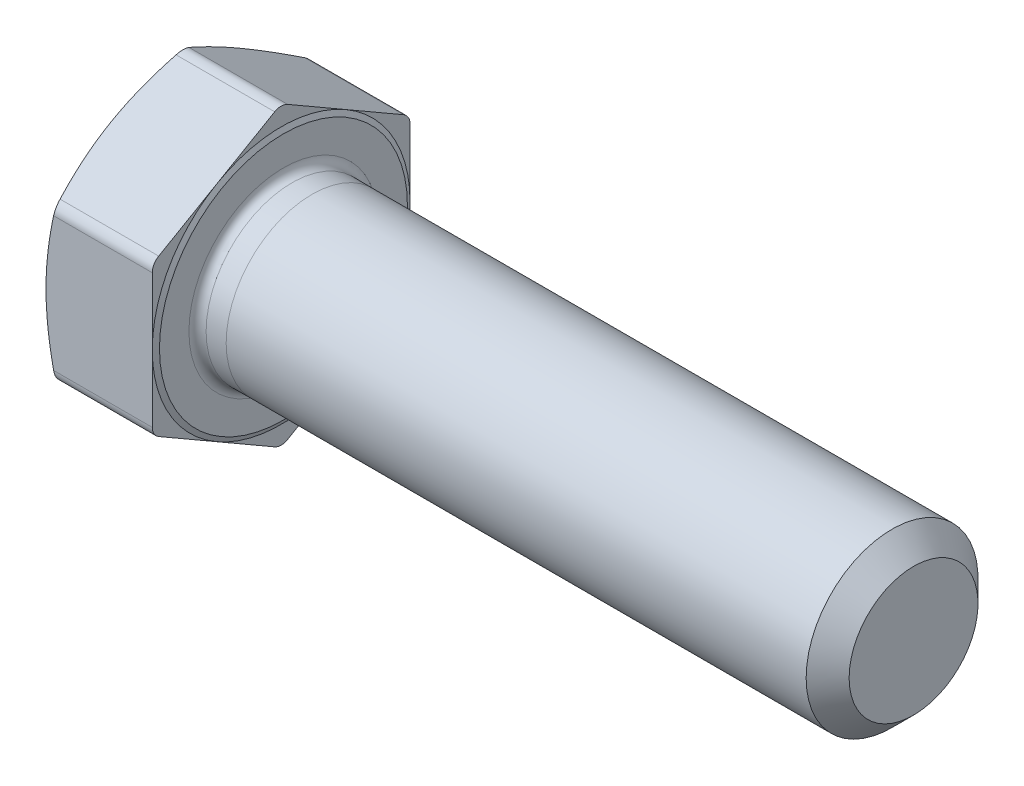
SolidWorks part; units mm, degrees
ref_plane "Front Plane" through (0, 0, 0) normal (0, 0, 1) x (1, 0, 0)
ref_plane "Top Plane" through (0, 0, 0) normal (0, 1, 0) x (1, 0, 0)
ref_plane "Right Plane" through (0, 0, 0) normal (1, 0, 0) x (0, 0, -1)
sketch "Sketch1" plane through (0, 0, 0) normal (0, 0, 1) x (1, 0, 0)
  line L0 (0, 0) -> (34.925, 0) construction
  line L1 (0, 0) -> (-6.35, 0) construction
  line L2 (0, 7.1437) -> (0, -7.1437) construction
  line L3 (-6.35, 7.1437) -> (-6.35, -7.1438) construction
  line L4 (34.925, 4.7625) -> (34.925, -4.7625) construction
  line L8 (33.3375, 4.7625) -> (34.925, 4.7625) construction
  point P8 (33.3375, 0)
  point P11 (29.3687, -4.7625)
  point P12 (1.5875, 0)
  dimension "Head Height" = 6.35
  dimension "Head Width" = 14.2875
  dimension "Length" = 34.925
  dimension "Thread Size" = 9.525
  dimension "D1" = 5.5562
  dimension "Thread Pitch" = 1.5875
  dimension "D2" = 1.5875
sketch "Sketch2" plane through (0, 0, 0) normal (1, 0, 0) x (0, 0, -1)
  circle A0 centre (0, 0) radius 4.7625
extrude "Boss-Extrude1" add sketch "Sketch2" along normal up to vertex (34.925 mm away) up to point (34.925, 4.7625, 0)
sketch "Sketch3" plane through (0, 0, 0) normal (-1, 0, 0) x (0, 0, 1)
  line L0 (0, 8.2489) -> (0, 0) construction
  line L1 (0, 8.2489) -> (-7.1437, 4.1244)
  line L2 (-7.1437, 4.1244) -> (-7.1437, -4.1244)
  line L3 (-7.1437, -4.1244) -> (0, -8.2489)
  line L4 (0, -8.2489) -> (7.1437, -4.1244)
  line L5 (7.1437, -4.1244) -> (7.1438, 4.1244)
  line L6 (7.1438, 4.1244) -> (0, 8.2489)
  circle A0 centre (0, 0) radius 7.1437 construction
extrude "Boss-Extrude2" add sketch "Sketch3" along normal up to vertex (6.35 mm away) up to point (-6.35, 7.1437, 0)
sketch "Sketch5" plane through (-6.35, 0, 0) normal (-1, 0, 0) x (0, 0, 1)
  circle A0 centre (0, 0) radius 7.1437 construction
  circle A1 centre (0, 0) radius 7.1437 construction
  circle A2 centre (0, 0) radius 6.4294
  dimension "D1" = 0.7144
extrude "Cut-Extrude1" cut sketch "Sketch5" against normal up to vertex (6.35 mm away) draft 65 flip side to cut up to point (0, 0, 0)
sketch "Sketch11" plane through (-6.35, 0, 0) normal (-1, 0, 0) x (0, 0, 1)
  line L0 (0, 5.0721) -> (0, 3.1432) construction
  line L1 (0.2857, 5.0721) -> (0.2858, 3.1432)
  line L2 (-0.2858, 5.0721) -> (-0.2858, 3.1432)
  arc A0 (0.2857, 5.0721) -> (-0.2858, 5.0721) centre (0, 5.0721) ccw
  arc A1 (-0.2858, 3.1432) -> (0.2858, 3.1432) centre (0, 3.1432) ccw
  circle A2 centre (0, 0) radius 5.3578 construction
  circle A3 centre (0, 0) radius 2.8575 construction
  point P3 (0, 4.1077)
  dimension "D1" = 10.7156
  dimension "D2" = 5.715
  dimension "D3" = 0.5715
extrude "Boss-Extrude5" add sketch "Sketch11" along normal blind 0.0635
fillet "Fillet5" radius 0.0635 4 edges at (-6.4135, 4.1077, 0.2858) (-6.4135, 2.8575, 0) (-6.4135, 4.1077, -0.2858) (-6.4135, 5.3578, 0)
pattern_circular "CirPattern1" count 6 over 360 about axis through (0, 0, 0) along (-1, 0, 0) of "Boss-Extrude5", "Fillet5" reverse direction yes
fillet "Fillet7" radius 0.7144 6 edges at (-2.7508, -8.2489, 0) (-2.7508, -4.1244, -7.1437) (-2.7508, 4.1244, -7.1437) (-2.7508, 8.2489, 0) (-2.7508, -4.1244, 7.1437) (-2.7508, 4.1244, 7.1438)
chamfer "Chamfer1" distance 1.1906 angle 45 1 edges at (34.925, 0, -4.7625)
sketch "Sketch15" plane through (0, 0, 0) normal (0, 0, 1) x (1, 0, 0)
  line L0 (0, 6.8714) -> (-0.127, 7.1437)
  line L1 (0, 7.1437) -> (0, -7.1437) construction
  line L2 (-0.127, 7.1437) -> (-0.127, 8.2489)
  line L3 (-0.127, 8.2489) -> (0, 8.2489)
  line L4 (0, 8.2489) -> (0, 6.8714)
  dimension "D1" = 0.127
  dimension "D2" = 25
revolve "Cut-Revolve1" cut sketch "Sketch15" angle 360 about L1
fillet "Fillet4" radius 0.4763 1 edges at (0, 0, 4.7625)
sketch "Reference Sketch1" plane through (0, 0, 0) normal (1, 0, 0) x (0, 0, -1)
  line L1 (0, 8.2489) -> (-7.1437, 4.1244)
  line L2 (-7.1437, 4.1244) -> (-7.1438, -4.1244)
  line L3 (-7.1438, -4.1244) -> (0, -8.2489)
  line L4 (0, -8.2489) -> (7.1437, -4.1244)
  line L5 (7.1437, -4.1244) -> (7.1438, 4.1244)
  line L6 (7.1438, 4.1244) -> (0, 8.2489)
  circle A0 centre (0, 0) radius 7.1437 construction
  circle A1 centre (0, 0) radius 7.1438
sketch "Sketch12" plane through (34.925, 0, 0) normal (1, 0, 0) x (0, 0, -1)
  circle A1 centre (0, 0) radius 4.7625
ref_plane "Plane2" through (1.5875, 0, 0) normal (1, 0, 0) x (0, 0, -1)
split "Split1" trim tools "Plane2" bodies to split 126 116 resulting bodies 118 119
curve "Helix/Spiral2" pitch 1.5875 height 36.5125 radius 4.7625 centre (34.925, 0, 0) axis (-1, 0, 0) start towards (0, 1, 0) parameters "Pitch"=1.5875
equation "\"D1@Sketch11\"=\"Head Width@Sketch1\" * 0.75"
equation "\"D2@Sketch11\"=\"Head Width@Sketch1\"*0.4"
equation "\"D3@Sketch11\"=\"Head Width@Sketch1\" * .04"
equation "\"D3@Helix/Spiral2\"=\"Length@Sketch1\" + \"Thread Pitch@Sketch1\""
equation "\"D1@Chamfer1\"=\"Thread Pitch@Sketch1\"*0.750"
equation "\"D1@Sketch1\"=\"Thread Pitch@Sketch1\"*3.5"
equation "\"Pitch@Helix/Spiral2\"=\"Thread Pitch@Sketch1\""
equation "\"D1@Sketch13\"=\"Thread Pitch@Sketch1\"*0.125"
equation "\"D1@Sketch5\"=\"Head Width@Sketch1\"*0.05"
equation "\"D1@Fillet4\"=\"Thread Size@Sketch1\"*0.05"
equation "\"D2@Sketch1\"=\"Thread Pitch@Sketch1\""
equation "\"D1@Fillet7\"=\"Head Width@Sketch1\"*0.05"
